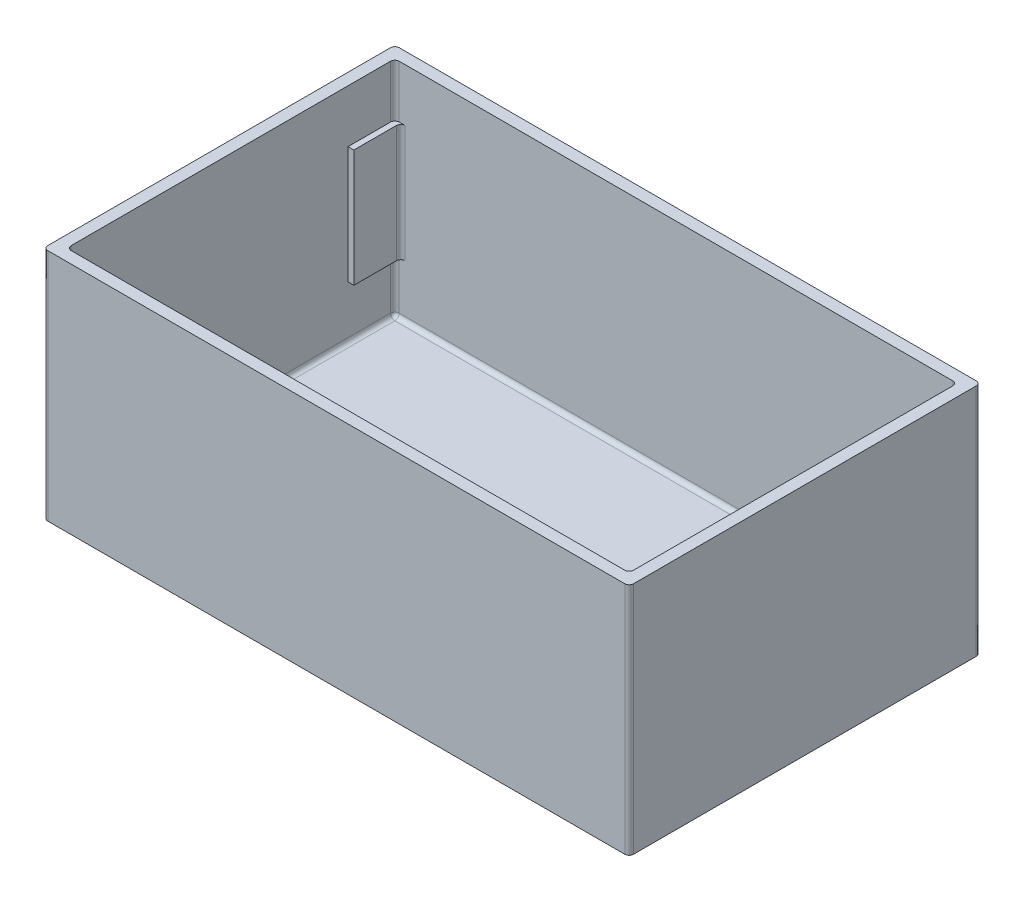
SolidWorks part; units mm, degrees
material "Alloy Steel"
ref_plane "Front Plane" through (0, 0, 0) normal (0, 0, 1) x (1, 0, 0)
ref_plane "Top Plane" through (0, 0, 0) normal (0, 1, 0) x (1, 0, 0)
ref_plane "Right Plane" through (0, 0, 0) normal (1, 0, 0) x (0, 0, -1)
sketch "Sketch10" plane through (0, 0, 0) normal (0, 1, 0) x (1, 0, 0)
  line L1 (-50, -30) -> (50, -30)
  line L2 (-50, -30) -> (-50, 30)
  line L3 (-50, 30) -> (50, 30)
  line L4 (50, -30) -> (50, 30)
  line L5 (-50, -30) -> (50, 30) construction
  line L6 (-50, 30) -> (50, -30) construction
  point P0 (0, 0)
  dimension "D1" = 100
  dimension "D2" = 60
extrude "Boss-Extrude2" add sketch "Sketch10" along normal blind 40
shell "Shell1" thickness 2 removed face at (0, 40, 0)
sketch "Sketch11" plane through (-48, 0, 0) normal (1, 0, 0) x (0, 0, -1)
  line L0 (28, 21) -> (-28, 21) construction
  line L1 (28, 40) -> (28, 2) construction
  line L2 (28, 21) -> (28, 31) construction
  line L3 (0, 21) -> (0, 40) construction
  line L4 (28, 31) -> (20, 31)
  line L5 (28, 31) -> (28, 11)
  line L6 (28, 11) -> (20, 11)
  line L7 (20, 31) -> (20, 11)
  line L10 (-28, 11) -> (-20, 11)
  line L11 (-20, 31) -> (-20, 11)
  line L12 (-28, 31) -> (-20, 31)
  line L13 (-28, 31) -> (-28, 11)
  dimension "D1" = 56
  dimension "D2" = 10
  dimension "D3" = 20
  dimension "D4" = 8
extrude "Boss-Extrude3" add sketch "Sketch11" along normal blind 1
fillet "Fillet1" radius 0.75 2 edges at (-47, 21, 28) (-47, 21, -28)
mirror "Mirror1" about plane through (0, 0, 0) normal (1, 0, 0) of "Boss-Extrude3"
fillet "Fillet2" radius 0.75 2 edges at (47, 21, 28) (47, 21, -28)
fillet "Fillet3" radius 0.75 4 edges at (0, 2, 28) (-48, 2, 0) (0, 2, -28) (48, 2, 0)
fillet "Fillet4" radius 0.75 4 edges at (-50, 20, -30) (-50, 20, 30) (50, 20, 30) (50, 20, -30)
fillet "Fillet5" radius 0.75 12 edges at (-47.7803, 2.2197, -27.7803) (-47.7803, 2.2197, 27.7803) (47.7803, 2.2197, -27.7803) (47.7803, 2.2197, 27.7803) (-48, 35.5, -28) (-48, 6.875, -28) (-48, 35.5, 28) (-48, 6.875, 28) (48, 35.5, -28) (48, 6.875, -28) (48, 35.5, 28) (48, 6.875, 28)
